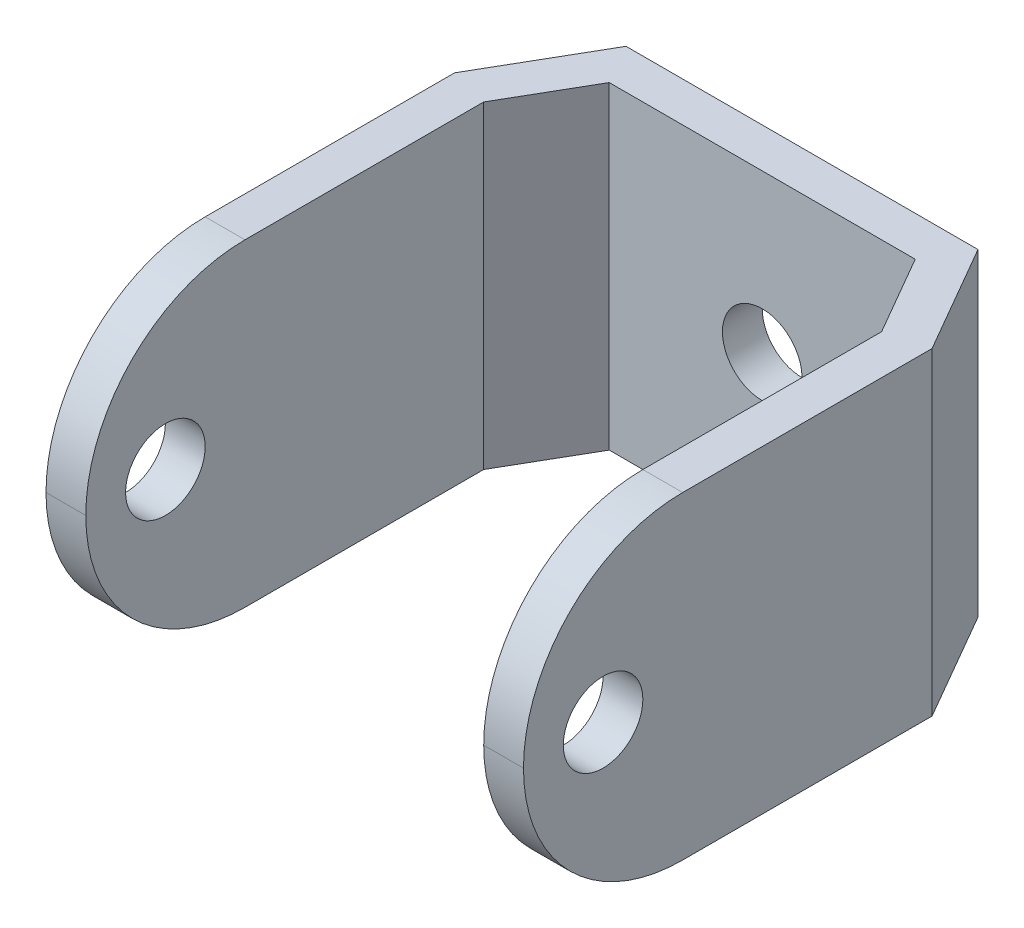
SolidWorks part; units mm, degrees
ref_plane "Front Plane" through (0, 0, 0) normal (0, 0, 1) x (1, 0, 0)
ref_plane "Top Plane" through (0, 0, 0) normal (0, 1, 0) x (1, 0, 0)
ref_plane "Right Plane" through (0, 0, 0) normal (1, 0, 0) x (0, 0, -1)
sketch "Sketch2" plane through (0, 0, 0) normal (0, 1, 0) x (1, 0, 0)
  line L0 (-30, 0) -> (-30, 51.3397)
  line L1 (-30, 51.3397) -> (-22.1132, 65)
  line L2 (-22.1132, 65) -> (22.1132, 65)
  line L3 (22.1132, 65) -> (30, 51.3397)
  line L4 (30, 51.3397) -> (30, 0)
  line L5 (30, 0) -> (25, 0)
  line L6 (25, 0) -> (25, 50)
  line L7 (25, 50) -> (19.2265, 60)
  line L8 (19.2265, 60) -> (-19.2265, 60)
  line L9 (-19.2265, 60) -> (-25, 50)
  line L10 (-25, 50) -> (-25, 0)
  line L11 (-25, 0) -> (-30, 0)
  point P14 (0, 60)
  point P16 (0, 65)
  dimension "D1" = 5
  dimension "D2" = 5
  dimension "D3" = 50
  dimension "D4" = 10
  dimension "D5" = 50
  dimension "D6" = 5
  dimension "D7" = 150
extrude "Boss-Extrude1" add sketch "Sketch2" along normal blind 40
sketch "Sketch3" plane through (30, 0, 0) normal (1, 0, 0) x (0, 0, -1)
  line L0 (0, 40) -> (51.3397, 40) construction
  line L2 (0, 40) -> (0, 0) construction
  circle A0 centre (10, 20) radius 5
  dimension "D1" = 10
  dimension "D2" = 20
  dimension "D3" = 10
extrude "Cut-Extrude1" cut sketch "Sketch3" against normal through all
fillet "Fillet1" radius 20 4 edges at (27.5, 40, 0) (-27.5, 40, 0) (-27.5, 0, 0) (27.5, 0, 0)
sketch "Sketch4" plane through (0, 0, -65) normal (0, 0, -1) x (-1, 0, 0)
  line L0 (-22.1132, 40) -> (-22.1132, 0) construction
  circle A0 centre (0, 20) radius 5
  point P6 (-22.1132, 20)
  dimension "D1" = 10
extrude "Cut-Extrude2" cut sketch "Sketch4" against normal up to next
